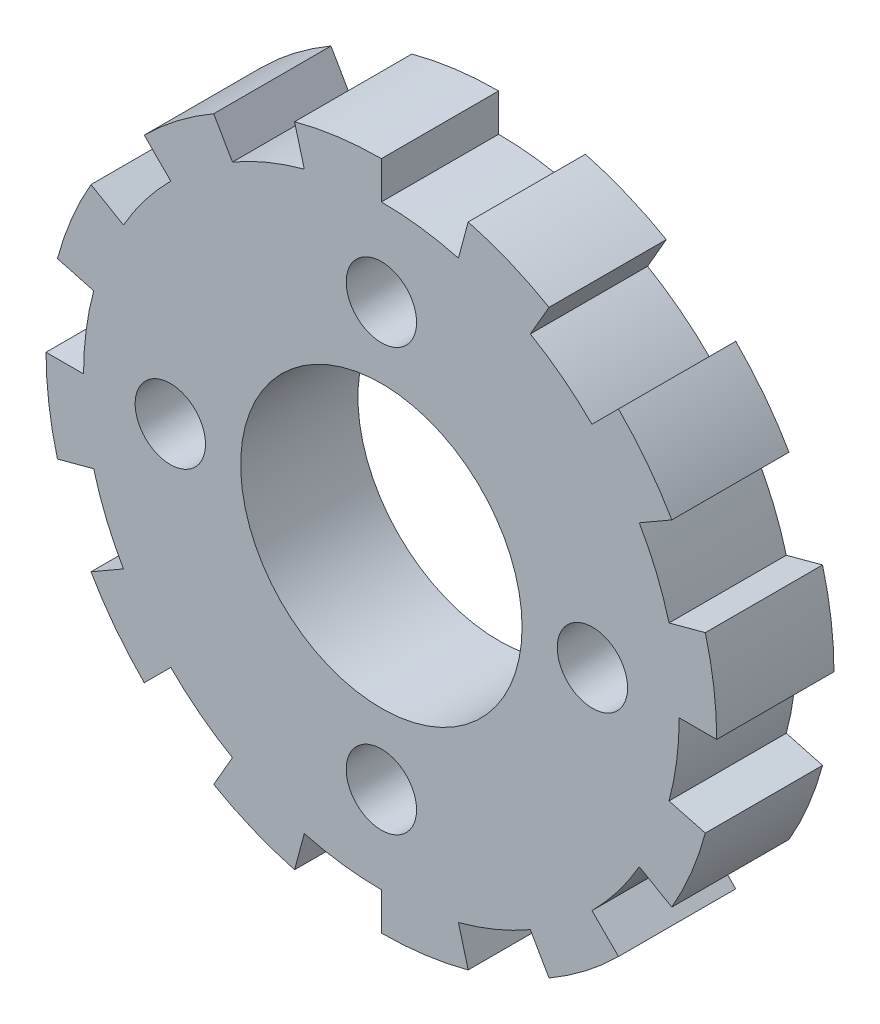
SolidWorks part; units mm, degrees
ref_plane "前视基准面" through (0, 0, 0) normal (0, 0, 1) x (1, 0, 0)
ref_plane "上视基准面" through (0, 0, 0) normal (0, 1, 0) x (1, 0, 0)
ref_plane "右视基准面" through (0, 0, 0) normal (1, 0, 0) x (0, 0, -1)
sketch "草图1" plane through (0, 0, 0) normal (0, 0, 1) x (1, 0, 0)
  line L1 (21.997, -12.7) -> (24.7683, -14.3)
  line L3 (25.4, 0) -> (28.6, 0)
  line L4 (24.5345, 6.574) -> (27.6255, 7.4022)
  line L6 (24.5345, -6.574) -> (27.6255, -7.4022)
  line L7 (12.7, -21.997) -> (14.3, -24.7683)
  line L8 (17.9605, -17.9605) -> (20.2233, -20.2233)
  line L9 (0, -25.4) -> (0, -28.6)
  line L10 (6.574, -24.5345) -> (7.4022, -27.6255)
  line L11 (-12.7, -21.997) -> (-14.3, -24.7683)
  line L12 (-6.574, -24.5345) -> (-7.4022, -27.6255)
  line L13 (-21.997, -12.7) -> (-24.7683, -14.3)
  line L14 (-17.9605, -17.9605) -> (-20.2233, -20.2233)
  line L15 (-25.4, 0) -> (-28.6, 0)
  line L16 (-24.5345, -6.574) -> (-27.6255, -7.4022)
  line L17 (-21.997, 12.7) -> (-24.7683, 14.3)
  line L18 (-24.5345, 6.574) -> (-27.6255, 7.4022)
  line L19 (-12.7, 21.997) -> (-14.3, 24.7683)
  line L20 (-17.9605, 17.9605) -> (-20.2233, 20.2233)
  line L21 (0, 25.4) -> (0, 28.6)
  line L22 (-6.574, 24.5345) -> (-7.4022, 27.6255)
  line L23 (12.7, 21.997) -> (14.3, 24.7683)
  line L24 (6.574, 24.5345) -> (7.4022, 27.6255)
  line L25 (21.997, 12.7) -> (24.7683, 14.3)
  line L26 (17.9605, 17.9605) -> (20.2233, 20.2233)
  circle A0 centre (0, 0) radius 12
  arc A1 (28.6, 0) -> (27.6255, 7.4022) centre (0, 0) ccw
  arc A2 (24.5345, 6.574) -> (21.997, 12.7) centre (0, 0) ccw
  arc A3 (24.7683, -14.3) -> (27.6255, -7.4022) centre (0, 0) ccw
  arc A4 (24.5345, -6.574) -> (25.4, 0) centre (0, 0) ccw
  arc A5 (14.3, -24.7683) -> (20.2233, -20.2233) centre (0, 0) ccw
  arc A6 (17.9605, -17.9605) -> (21.997, -12.7) centre (0, 0) ccw
  arc A7 (0, -28.6) -> (7.4022, -27.6255) centre (0, 0) ccw
  arc A8 (6.574, -24.5345) -> (12.7, -21.997) centre (0, 0) ccw
  arc A9 (-14.3, -24.7683) -> (-7.4022, -27.6255) centre (0, 0) ccw
  arc A10 (-6.574, -24.5345) -> (0, -25.4) centre (0, 0) ccw
  arc A11 (-24.7683, -14.3) -> (-20.2233, -20.2233) centre (0, 0) ccw
  arc A12 (-17.9605, -17.9605) -> (-12.7, -21.997) centre (0, 0) ccw
  arc A13 (-28.6, 0) -> (-27.6255, -7.4022) centre (0, 0) ccw
  arc A14 (-24.5345, -6.574) -> (-21.997, -12.7) centre (0, 0) ccw
  arc A15 (-24.7683, 14.3) -> (-27.6255, 7.4022) centre (0, 0) ccw
  arc A16 (-24.5345, 6.574) -> (-25.4, 0) centre (0, 0) ccw
  arc A17 (-14.3, 24.7683) -> (-20.2233, 20.2233) centre (0, 0) ccw
  arc A18 (-17.9605, 17.9605) -> (-21.997, 12.7) centre (0, 0) ccw
  arc A19 (0, 28.6) -> (-7.4022, 27.6255) centre (0, 0) ccw
  arc A20 (-6.574, 24.5345) -> (-12.7, 21.997) centre (0, 0) ccw
  arc A21 (14.3, 24.7683) -> (7.4022, 27.6255) centre (0, 0) ccw
  arc A22 (6.574, 24.5345) -> (0, 25.4) centre (0, 0) ccw
  arc A23 (24.7683, 14.3) -> (20.2233, 20.2233) centre (0, 0) ccw
  arc A24 (17.9605, 17.9605) -> (12.7, 21.997) centre (0, 0) ccw
  point P11 (0, 0)
  point P67 (0, 0)
  dimension "D1" = 12
extrude "凸台-拉伸1" add sketch "草图1" along normal blind 5 and the other way blind 5
sketch "草图2" plane through (0, 0, 0) normal (0, 0, 1) x (1, 0, 0)
  circle A1 centre (18, 0) radius 3
  circle A2 centre (0, -18) radius 3
  circle A3 centre (-18, 0) radius 3
  circle A4 centre (0, 18) radius 3
  point P12 (0, 0)
  dimension "D1" = 4
extrude "切除-拉伸1" cut sketch "草图2" against normal blind 10 and the other way blind 10
